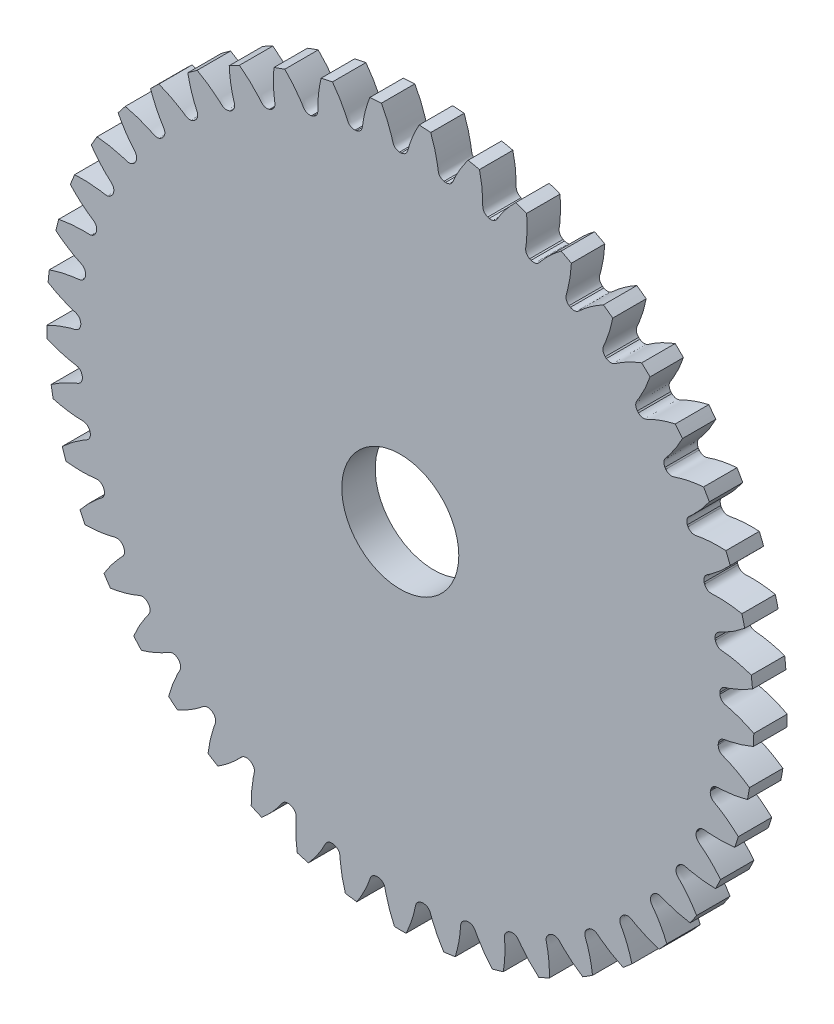
SolidWorks part; units mm, degrees
ref_plane "前视基准面" through (0, 0, 0) normal (0, 0, 1) x (1, 0, 0)
ref_plane "上视基准面" through (0, 0, 0) normal (0, 1, 0) x (1, 0, 0)
ref_plane "右视基准面" through (0, 0, 0) normal (1, 0, 0) x (0, 0, -1)
other "Configuration Table"
sketch "草图1" plane through (0, 0, 0) normal (0, 0, 1) x (1, 0, 0)
  circle A0 centre (0, 0) radius 10.575
extrude "凸台-拉伸1" add sketch "草图1" along normal blind 1
ref_axis "基准轴1" through (0, 0, 1) along (0, 0, -1)
sketch "草图2" plane through (0, 0, 0) normal (0, 0, 1) x (1, 0, 0)
  line L0 (0, 0) -> (0, 10.575) construction
  circle A0 centre (0, 0) radius 10.575 construction
  arc A1 (0.0233, 9.5625) -> (-0.0233, 9.5625) centre (0, 0) ccw
  arc A2 (1.7228, 12.0175) -> (-1.7228, 12.0175) centre (0, 0) ccw
  spline S0 degree 3 poles (0.0233, 9.5625) (0.1996, 9.5868) (0.2196, 9.7176) (0.2613, 9.8593) (0.2773, 9.9107) (0.2956, 9.9653) (0.3162, 10.0231) (0.3393, 10.084) (0.3651, 10.148) (0.3937, 10.215) (0.4251, 10.2849) (0.4596, 10.3575) (0.4972, 10.4329) (0.538, 10.5109) (0.5823, 10.5913) (0.63, 10.6742) (0.6814, 10.7593) (0.7365, 10.8467) (0.7954, 10.9361) (0.8583, 11.0274) (0.9252, 11.1205) (0.9962, 11.2154) (1.0714, 11.3118) (1.151, 11.4096) (1.2349, 11.5087) (1.3233, 11.609) (1.4163, 11.7103) (1.5483, 11.8483) (1.6517, 11.9502) (1.7228, 12.0175) knots 0 0 0 0 0.112268 0.128789 0.146568 0.165606 0.185901 0.207456 0.230268 0.254339 0.279668 0.306255 0.334101 0.363205 0.393567 0.425188 0.458067 0.492204 0.527599 0.564253 0.602166 0.641336 0.681765 0.723452 0.766398 0.810601 0.856064 0.902784 1 1 1 1
  spline S1 degree 3 poles (-0.0233, 9.5625) (-0.1996, 9.5868) (-0.2196, 9.7176) (-0.2613, 9.8593) (-0.2773, 9.9107) (-0.2956, 9.9653) (-0.3162, 10.0231) (-0.3393, 10.084) (-0.3651, 10.148) (-0.3937, 10.215) (-0.4251, 10.2849) (-0.4596, 10.3575) (-0.4972, 10.4329) (-0.538, 10.5109) (-0.5823, 10.5913) (-0.63, 10.6742) (-0.6814, 10.7593) (-0.7365, 10.8467) (-0.7954, 10.9361) (-0.8583, 11.0274) (-0.9252, 11.1205) (-0.9962, 11.2154) (-1.0714, 11.3118) (-1.151, 11.4096) (-1.2349, 11.5087) (-1.3233, 11.609) (-1.4163, 11.7103) (-1.5483, 11.8483) (-1.6517, 11.9502) (-1.7228, 12.0175) knots 0 0 0 0 0.112268 0.128789 0.146568 0.165606 0.185901 0.207456 0.230268 0.254339 0.279668 0.306255 0.334101 0.363205 0.393567 0.425188 0.458067 0.492204 0.527599 0.564253 0.602166 0.641336 0.681765 0.723452 0.766398 0.810601 0.856064 0.902784 1 1 1 1
extrude "切除-拉伸1" cut sketch "草图2" along normal through all
pattern_circular "阵列(圆周)1" count 45 every 8 about axis through (0, 0, 1) along (0, 0, -1) of "切除-拉伸1"
sketch "草图3" plane through (0, 0, 0) normal (0, 0, 1) x (1, 0, 0)
  circle A0 centre (0, 0) radius 10.125 construction
  dimension "Dn" = 20.25
sketch "草图4" plane through (0, 0, 1) normal (0, 0, 1) x (1, 0, 0)
  circle A0 centre (0, 0) radius 1.75
  dimension "D1" = 3.5
extrude "切除-拉伸2" cut sketch "草图4" against normal through all
